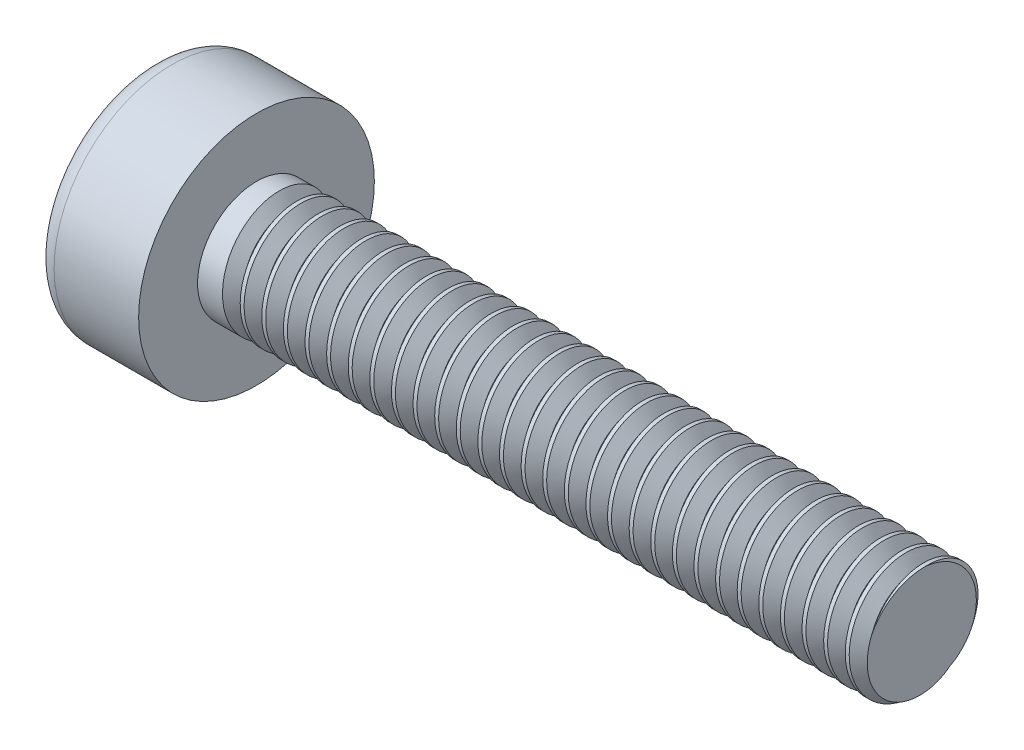
SolidWorks part; units mm, degrees
ref_plane "Front Plane" through (0, 0, 0) normal (0, 0, 1) x (1, 0, 0)
ref_plane "Top Plane" through (0, 0, 0) normal (0, 1, 0) x (1, 0, 0)
ref_plane "Right Plane" through (0, 0, 0) normal (1, 0, 0) x (0, 0, -1)
sketch "Sketch1" plane through (0, 0, 0) normal (0, 0, 1) x (1, 0, 0)
  line L1 (0, 3) -> (34, 3)
  line L2 (34, 3) -> (34, 0)
  line L3 (34, 0) -> (0, 0)
  line L4 (0, 3) -> (0, 6)
  line L5 (0, 6) -> (-5, 6)
  line L6 (-5.5, 0) -> (0, 0)
  arc A0 (-5, 6) -> (-5.5, 0) centre (4.2532, 2.2081) ccw
  dimension "D5" = 10
  dimension "D1" = 3
  dimension "D2" = 5.5
  dimension "D3" = 5
  dimension "D4" = 3
revolve "Revolve1" add sketch "Sketch1" angle 360 about L3
ref_plane "Plane1" through (-6, 0, 0) normal (1, 0, 0) x (0, 0, -1)
sketch "Sketch4" plane through (-6, 0, 0) normal (1, 0, 0) x (0, 0, -1)
  line L0 (-3.6, 0.71) -> (-3.6, -0.71)
  line L1 (0.71, 3.6) -> (-0.71, 3.6)
  line L2 (-3.6, 0.71) -> (-1.4338, 0.71)
  line L3 (-3.6, -0.71) -> (-1.4338, -0.71)
  line L4 (0.71, 3.6) -> (0.71, 1.4338)
  line L5 (-0.71, 3.6) -> (-0.71, 1.4338)
  line L6 (3.6, -0.71) -> (3.6, 0.71)
  line L7 (3.6, -0.71) -> (1.4338, -0.71)
  line L8 (3.6, 0.71) -> (1.4338, 0.71)
  line L9 (-0.71, -3.6) -> (0.71, -3.6)
  line L10 (-0.71, -3.6) -> (-0.71, -1.4338)
  line L11 (0.71, -3.6) -> (0.71, -1.4338)
  arc A0 (-0.71, 1.4338) -> (-1.4338, 0.71) centre (0, 0) ccw
  arc A2 (-1.4338, -0.71) -> (-0.71, -1.4338) centre (0, 0) ccw
  arc A3 (0.71, -1.4338) -> (1.4338, -0.71) centre (0, 0) ccw
  arc A4 (1.4338, 0.71) -> (0.71, 1.4338) centre (0, 0) ccw
  point P6 (-3.6, 0)
  point P23 (0, 0)
  dimension "D1" = 1.42
  dimension "D3" = 3.2
  dimension "D2" = 4
extrude "Cut-Extrude1" cut sketch "Sketch4" along normal blind 3.5 draft 10 contours L11 A3 L7 L6 L8 A4 L4 L1 L5 A0 L2 L0 L3 A2 L10 L9
sketch "Sketch5" plane through (34, 0, 0) normal (1, 0, 0) x (0, 0, -1)
  circle A1 centre (0, 0) radius 3
  circle A2 centre (0, 0) radius 3
  dimension "D1" = 0
curve "Helix/Spiral1" pitch 1.1 height 33.5 turns 30.4545
sketch "Sketch6" plane through (0, 0, 0) normal (0, 0, 1) x (1, 0, 0)
  line L0 (34, 3) -> (34.9, 3)
  line L1 (34.9, 3) -> (34.45, 2.4)
  line L2 (34.45, 2.4) -> (34, 3)
  point P3 (34.45, 3)
  dimension "D1" = 0.9
  dimension "D2" = 0.6
sweep "Cut-Sweep1" cut profiles "Sketch6" path "Helix/Spiral1" align with end faces yes
fillet "Fillet2" radius 1 1 edges at (-5, 0, -6)
sketch "Sketch7" plane through (0, 0, 0) normal (0, 0.2817, -0.9595) x (-1, 0, 0)
  line L3 (-0.9495, -2.4) -> (-1.3995, -3)
  line L4 (-1.3995, -3) -> (-0.4995, -3)
  line L5 (-0.4995, -3) -> (-0.9495, -2.4)
  line L6 (-0.9495, -2.4) -> (-1.3995, -3)
  line L7 (-1.3995, -3) -> (-0.4995, -3)
  line L8 (-0.4995, -3) -> (-0.9495, -2.4)
  dimension "D1" = 0
extrude "Cut-Extrude2" cut sketch "Sketch7" against normal blind 3.5
